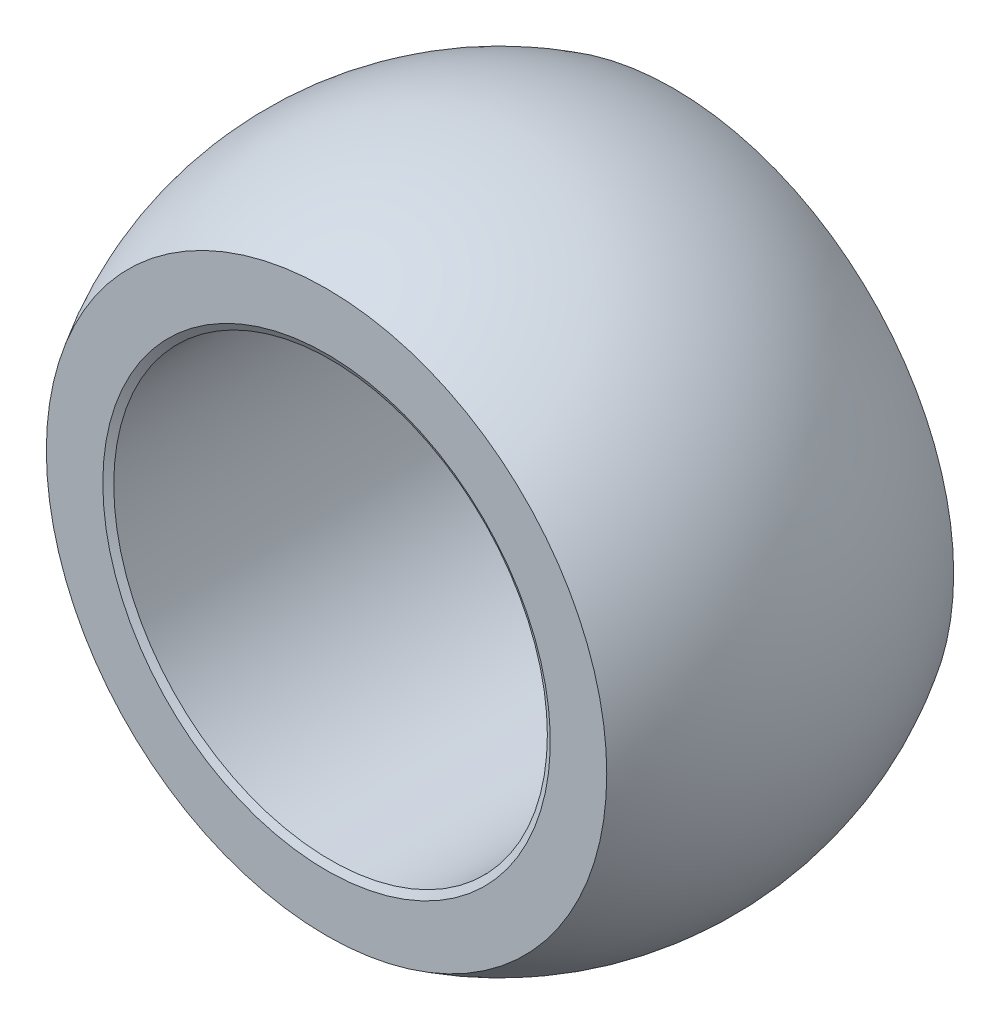
SolidWorks part; units mm, degrees
ref_plane "Front Plane" through (0, 0, 0) normal (0, 0, 1) x (1, 0, 0)
ref_plane "Top Plane" through (0, 0, 0) normal (0, 1, 0) x (1, 0, 0)
ref_plane "Right Plane" through (0, 0, 0) normal (1, 0, 0) x (0, 0, -1)
sketch "Sketch1" plane through (0, 0, 0) normal (0, 0, 1) x (1, 0, 0)
  line L0 (0, 12.065) -> (0, -12.065) construction
  line L1 (0, 12.065) -> (0, -12.065)
  arc A0 (0, 12.065) -> (0, -12.065) centre (0, 0) cw
  point P3 (0, 0)
  dimension "D1" = 12.065
revolve "Revolve1" add sketch "Sketch1" angle 360 about L0
sketch "Sketch2" plane through (0, 0, 0) normal (1, 0, 0) x (0, 0, -1)
  line L0 (-6.35, 10.2587) -> (-6.35, -10.2587)
  line L1 (0, 15.6767) -> (0, -15.1875) construction
  line L2 (6.35, 10.2587) -> (6.35, -10.2587)
  circle A0 centre (0, 0) radius 12.065 construction
  arc A1 (-6.35, 10.2587) -> (-6.35, -10.2587) centre (0, 0) ccw
  arc A2 (6.35, -10.2587) -> (6.35, 10.2587) centre (0, 0) ccw
  dimension "D1" = 12.7
extrude "Cut-Extrude1" cut sketch "Sketch2" against normal through all both and the other way through all
sketch "Sketch3" plane through (0, 0, 6.35) normal (0, 0, 1) x (1, 0, 0)
  circle A0 centre (0, 0) radius 7.9375
  dimension "D1" = 15.875
extrude "Cut-Extrude2" cut sketch "Sketch3" against normal through all
chamfer "Chamfer1" distance 0.254 angle 30 1 edges at (7.9375, 0, 6.35) first distance on face at (7.9375, 0, 6.35)
